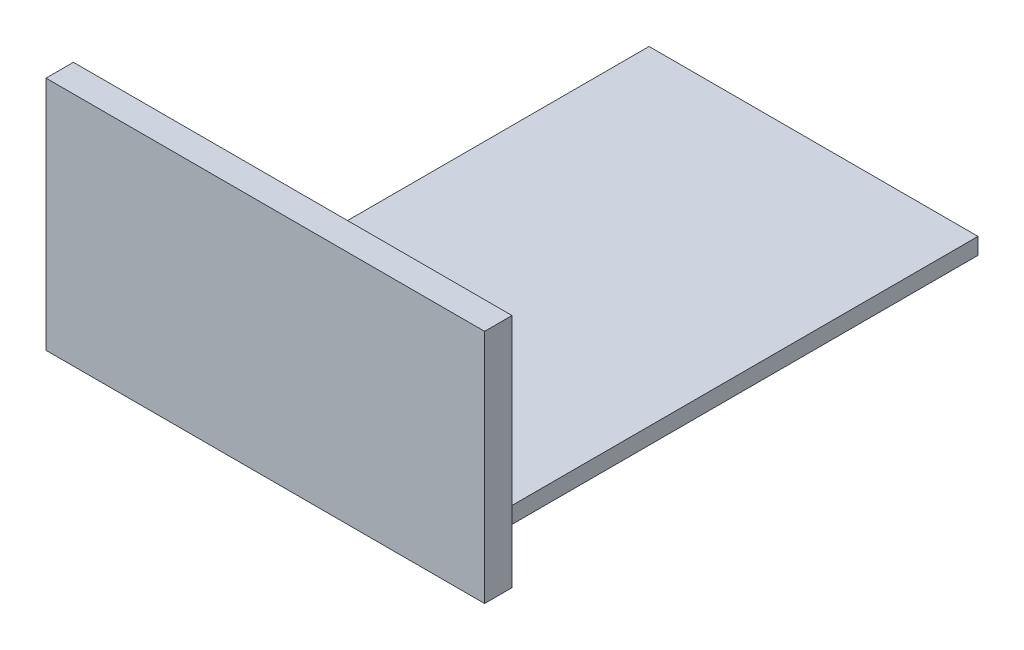
SolidWorks part; units mm, degrees
ref_plane "Спереди" through (0, 0, 0) normal (0, 0, 1) x (1, 0, 0)
ref_plane "Сверху" through (0, 0, 0) normal (0, 1, 0) x (1, 0, 0)
ref_plane "Справа" through (0, 0, 0) normal (1, 0, 0) x (0, 0, -1)
sketch "Эскиз1" plane through (0, 0, 0) normal (0, 1, 0) x (1, 0, 0)
  line L1 (30, 50) -> (-30, 50)
  line L2 (30, 50) -> (30, -50)
  line L3 (30, -50) -> (-30, -50)
  line L4 (-30, 50) -> (-30, -50)
  line L5 (30, 50) -> (-30, -50) construction
  line L6 (30, -50) -> (-30, 50) construction
  point P0 (0, 0)
  dimension "D1" = 100
  dimension "D2" = 60
extrude "Бобышка-Вытянуть1" add sketch "Эскиз1" along normal blind 3
sketch "Эскиз2" plane through (0, 3, 0) normal (0, 1, 0) x (1, 0, 0)
  line L0 (-30, -50) -> (30, -50) construction
  line L1 (-40, -50) -> (40, -50)
  line L2 (-40, -50) -> (-40, -45)
  line L3 (-40, -45) -> (40, -45)
  line L4 (40, -50) -> (40, -45)
  line L5 (-40, -47.5) -> (-30, -47.5) construction
  line L6 (-30, 50) -> (-30, -50) construction
  line L7 (-30, -47.5) -> (30, -47.5) construction
  line L8 (30, -50) -> (30, 50) construction
  line L9 (30, -47.5) -> (40, -47.5) construction
  dimension "D1" = 80
  dimension "D2" = 5
extrude "Бобышка-Вытянуть2" add sketch "Эскиз2" along normal blind 40 and the other way blind 3
fillet "Скругление1" radius 10 2 edges at (30, 1.5, 45) (-30, 1.5, 45)
